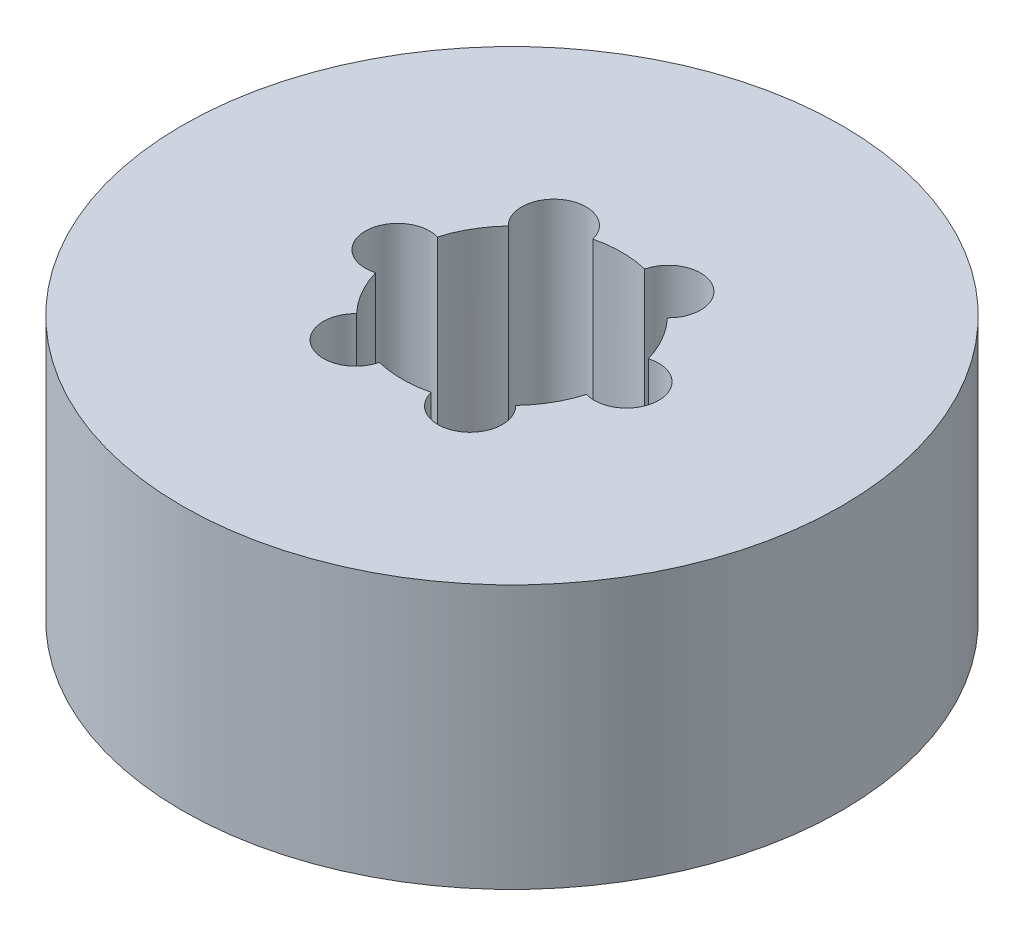
SolidWorks part; units mm, degrees
ref_plane "Front Plane" through (0, 0, 0) normal (0, 0, 1) x (1, 0, 0)
ref_plane "Top Plane" through (0, 0, 0) normal (0, 1, 0) x (1, 0, 0)
ref_plane "Right Plane" through (0, 0, 0) normal (1, 0, 0) x (0, 0, -1)
sketch "Sketch1" plane through (0, 0, 0) normal (0, 1, 0) x (1, 0, 0)
  circle A0 centre (0, 0) radius 30
  dimension "FLANGE_OD" = 60
extrude "Boss-Extrude1" add sketch "Sketch1" along normal blind 24
sketch "Sketch2" plane through (0, 0, 0) normal (0, 1, 0) x (1, 0, 0)
  circle A0 centre (0, 0) radius 10
  dimension "BORE_D" = 20
extrude "Cut-Extrude1" cut sketch "Sketch2" along normal through all
sketch "Sketch3" plane through (0, 24, 0) normal (0, 1, 0) x (1, 0, 0)
  circle A0 centre (0, 0) radius 10.4171 construction
  circle A1 centre (-10.4171, 0) radius 2.9316
  dimension "BOLT_D" = 5.8631
  dimension "BOLT_PCD" = 20.8342
extrude "Cut-Extrude2" cut sketch "Sketch3" against normal blind 20.8748
pattern_circular "CirPattern1" count 6 over 360 about axis through (0, 0, 0) along (0, 1, 0) of "Cut-Extrude2"
